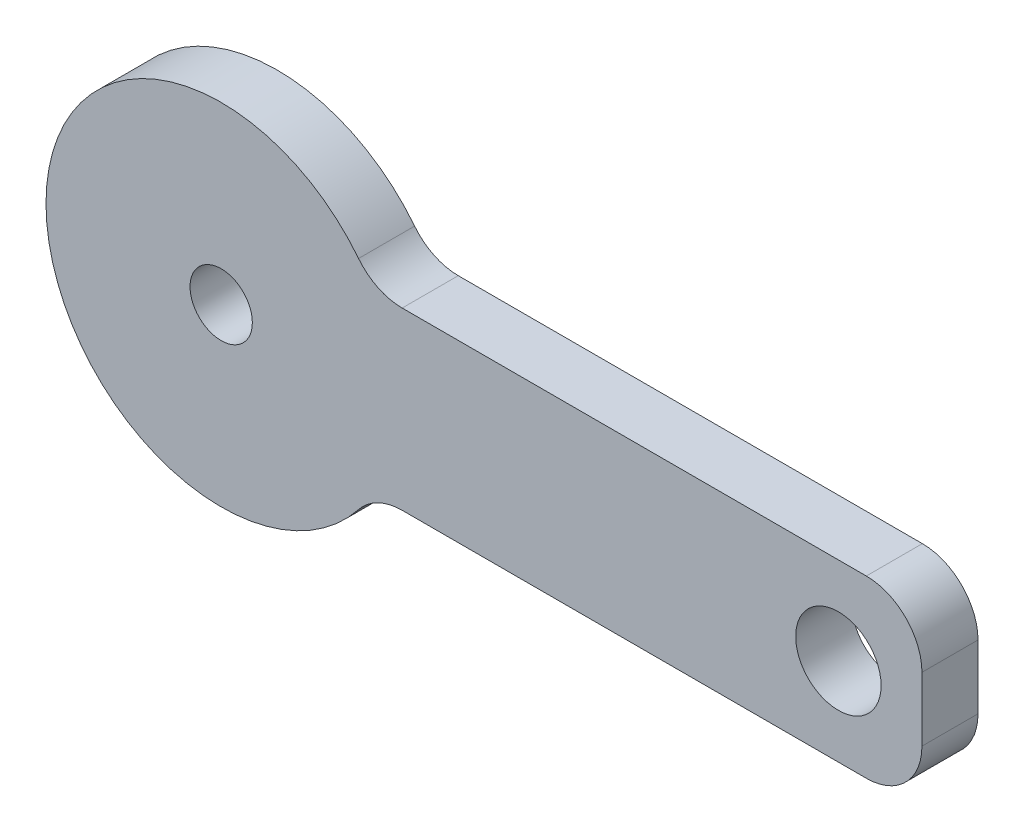
SolidWorks part; units mm, degrees
material "6061-T4 (SS)"
ref_plane "Front Plane" through (0, 0, 0) normal (0, 0, 1) x (1, 0, 0)
ref_plane "Top Plane" through (0, 0, 0) normal (0, 1, 0) x (1, 0, 0)
ref_plane "Right Plane" through (0, 0, 0) normal (1, 0, 0) x (0, 0, -1)
sketch "Sketch1" plane through (0, 0, 0) normal (0, 0, 1) x (1, 0, 0)
  line L1 (5.166, -2.5) -> (18.4125, -2.5)
  line L3 (5.166, 2.5) -> (18.4125, 2.5)
  line L4 (20, -0.9125) -> (20, 0.9125)
  arc A0 (3.9211, 3.1025) -> (3.9211, -3.1025) centre (0, 0) ccw
  arc A1 (5.166, -2.5) -> (3.9211, -3.1025) centre (5.166, -4.0875) ccw
  arc A2 (5.166, 2.5) -> (3.9211, 3.1025) centre (5.166, 4.0875) cw
  arc A3 (18.4125, 2.5) -> (20, 0.9125) centre (18.4125, 0.9125) cw
  arc A4 (18.4125, -2.5) -> (20, -0.9125) centre (18.4125, -0.9125) ccw
  point P12 (20, 2.5)
  point P15 (20, -2.5)
  dimension "D2" = 10
  dimension "D4" = 1.5875
  dimension "D5" = 1.5875
  dimension "D1" = 20
  dimension "D3" = 5
extrude "Boss-Extrude1" add sketch "Sketch1" along normal blind 1.6002
hole_wizard "#0 Clearance Hole1" positions "Sketch2" profile "Sketch3" hole size "#0" standard "ANSI Inch" end condition through all
sketch "Sketch2" plane through (0, 0, 1.6002) normal (0, 0, 1) x (1, 0, 0)
  point P0 (0, 0)
sketch "Sketch3" plane through (0, 0, 1.6002) normal (1, 0, 0) x (0, -1, 0)
  line L0 (0, 0) -> (0, 1.6002)
  line L1 (0, 1.6002) -> (0.889, 1.6002)
  line L2 (0.889, 1.6002) -> (0.889, 0)
  line L5 (0.889, 0) -> (0, 0)
  line L11 (0, -6.35) -> (0, 107.95) construction
  dimension "Thru Hole Dia." = 1.778
  dimension "Thru Hole Depth" = 1.6002
hole_wizard "#2 Clearance Hole1" positions "Sketch4" profile "Sketch5" hole size "#2" standard "ANSI Inch" end condition through all
sketch "Sketch4" plane through (0, 0, 1.6002) normal (0, 0, 1) x (1, 0, 0)
  line L5 (17.6156, 2.5) -> (17.6156, -2.5) construction
  line L6 (18.4125, 2.5) -> (5.166, 2.5) construction
  line L7 (5.166, -2.5) -> (18.4125, -2.5) construction
  point P0 (17.6156, 0)
  point P45 (0, 0)
  point P50 (18.3544, 0)
sketch "Sketch5" plane through (17.6156, 0, 1.6002) normal (1, 0, 0) x (0, -1, 0)
  line L0 (0, 0) -> (0, 1.6002)
  line L1 (0, 1.6002) -> (1.2192, 1.6002)
  line L2 (1.2192, 1.6002) -> (1.2192, 0)
  line L5 (1.2192, 0) -> (0, 0)
  line L11 (0, -6.35) -> (0, 107.95) construction
  dimension "Thru Hole Dia." = 2.4384
  dimension "Thru Hole Depth" = 1.6002
